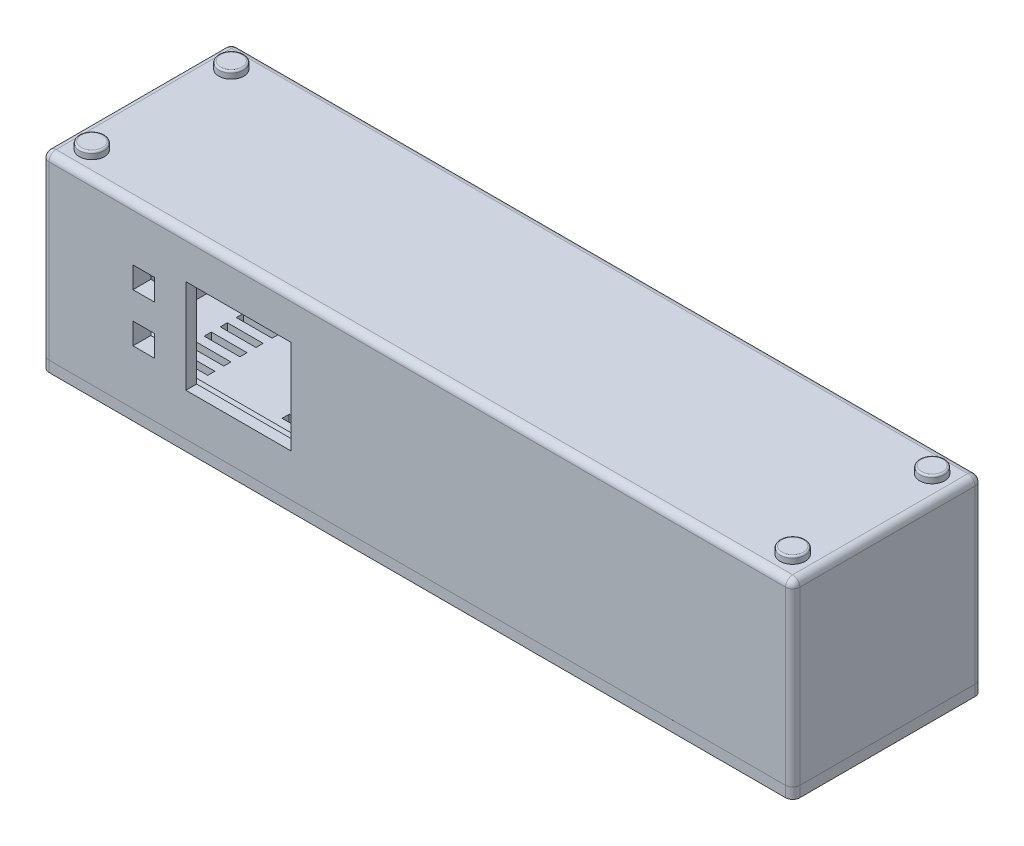
SolidWorks part; units mm, degrees
material "PET"
ref_plane "Спереди" through (0, 0, 0) normal (0, 0, 1) x (1, 0, 0)
ref_plane "Сверху" through (0, 0, 0) normal (0, 1, 0) x (1, 0, 0)
ref_plane "Справа" through (0, 0, 0) normal (1, 0, 0) x (0, 0, -1)
other "Configuration Table"
sketch "Основание & крышка" plane through (0, 0, 0) normal (0, 1, 0) x (1, 0, 0)
  line L1 (105, -26.5) -> (-105, -26.5)
  line L2 (105, -26.5) -> (105, 26.5)
  line L3 (105, 26.5) -> (-105, 26.5)
  line L4 (-105, -26.5) -> (-105, 26.5)
  line L5 (105, -26.5) -> (-105, 26.5) construction
  line L6 (105, 26.5) -> (-105, -26.5) construction
  line L7 (100, -21.5) -> (-100, -21.5)
  line L8 (100, -21.5) -> (100, 21.5)
  line L9 (100, 21.5) -> (-100, 21.5)
  line L10 (-100, -21.5) -> (-100, 21.5)
  line L11 (100, -21.5) -> (-100, 21.5) construction
  line L12 (100, 21.5) -> (-100, -21.5) construction
  point P0 (0, 0)
  point P5 (0, 0)
  dimension "D1" = 210
  dimension "D2" = 53
  dimension "D3" = 43
  dimension "D4" = 200
extrude "Бобышка-Вытянуть1" add sketch "Основание & крышка" along normal blind 50 contours L3 L4 L1 L2
sketch "Эскиз3" plane through (0, 0, 0) normal (0, -1, 0) x (1, 0, 0)
  line L0 (105, 26.5) -> (-105, 26.5) construction
  line L1 (-100, -21.5) -> (100, -21.5)
  line L2 (-100, -21.5) -> (-100, 21.5)
  line L3 (-100, 21.5) -> (100, 21.5)
  line L4 (100, -21.5) -> (100, 21.5)
  line L5 (-100, -21.5) -> (100, 21.5) construction
  line L6 (-100, 21.5) -> (100, -21.5) construction
  line L7 (105, 26.5) -> (105, -26.5) construction
  point P0 (0, 0)
  dimension "D1" = 5
  dimension "D2" = 5
extrude "Вырез-Вытянуть1" cut sketch "Эскиз3" against normal blind 45
sketch "Эскиз4" plane through (0, 50, 0) normal (0, 1, 0) x (1, 0, 0)
  line L0 (0, 41.131) -> (0, -55.5904) construction
  line L1 (105, 26.5) -> (-105, 26.5) construction
  line L2 (105, -26.5) -> (105, 26.5) construction
  line L3 (-127.2033, 0) -> (126.8125, 0) construction
  circle A0 centre (98, 19.5) radius 3.5
  circle A1 centre (-98, 19.5) radius 3.5
  circle A2 centre (98, -19.5) radius 3.5
  circle A3 centre (-98, -19.5) radius 3.5
  dimension "D1" = 7
  dimension "D3" = 7
  dimension "D2" = 7
sketch "Эскиз6" plane through (0, 50, 0) normal (0, 1, 0) x (1, 0, 0)
  line L0 (-117.6289, 0) -> (122.9046, 0) construction
  line L1 (0, 47.7745) -> (0, -57.5444) construction
extrude "Бобышка-Вытянуть2" add sketch "Эскиз4" along normal blind 2 draft 1 contours A0
fillet "Скругление2" radius 0.5 1 edges at (98, 52, -16.0349)
extrude "Бобышка-Вытянуть3" add sketch "Эскиз4<5>" along normal blind 2 contours A2
sketch "Эскиз4<5>" plane through (0, 50, 0) normal (0, 1, 0) x (1, 0, 0) same geometry as "Эскиз4"
extrude "Бобышка-Вытянуть4" add sketch "Эскиз4<6>" along normal blind 2 contours A3
sketch "Эскиз4<6>" plane through (0, 50, 0) normal (0, 1, 0) x (1, 0, 0) same geometry as "Эскиз4"
extrude "Бобышка-Вытянуть5" add sketch "Эскиз4<7>" along normal blind 2 contours A1
sketch "Эскиз4<7>" plane through (0, 50, 0) normal (0, 1, 0) x (1, 0, 0) same geometry as "Эскиз4"
fillet "Скругление3" radius 0.5 1 edges at (-98, 52, 23)
fillet "Скругление4" radius 0.5 1 edges at (-98, 52, -23)
fillet "Скругление5" radius 0.5 1 edges at (98, 52, 16)
sketch "Эскиз7" plane through (0, 0, -26.5) normal (0, 0, -1) x (-1, 0, 0)
  line L0 (0, -32.9698) -> (0, 82.1336) construction
  line L1 (-136.416, 24.5819) -> (136.5704, 24.5819) construction
  circle A0 centre (0, 35.0819) radius 6
  point P7 (0, 24.5819)
  dimension "D1" = 12
  dimension "D2" = 10.5
extrude "Вырез-Вытянуть2" cut sketch "Эскиз7" against normal blind 14 draft 5 contours A0
fillet "Скругление6" radius 2 1 edges at (-6, 35.0819, -26.5)
sketch "Эскиз8" plane through (0, 0, -21.5) normal (0, 0, 1) x (1, 0, 0)
  circle A0 centre (0, 35.0819) radius 7
  dimension "D1" = 14
extrude "Бобышка-Вытянуть6" add sketch "Эскиз8" along normal blind 7 draft 5 contours A0
sketch "Эскиз9" plane through (0, 0, -14.5) normal (0, 0, 1) x (1, 0, 0)
  circle A0 centre (0, 35.0819) radius 5.15
  dimension "D1" = 10.3
extrude "Вырез-Вытянуть3" cut sketch "Эскиз9" against normal blind 7 draft 5 draft outward yes
sketch "Эскиз10" plane through (0, 0, 26.5) normal (0, 0, 1) x (1, 0, 0)
  line L0 (0, -14.7722) -> (0, 61.6389) construction
  line L1 (-118.5615, 25) -> (116.6086, 25) construction
  line L2 (-127.2033, 50) -> (126.8125, 50) construction
  line L3 (-64.7, 38.15) -> (-35.3, 38.15)
  line L4 (-64.7, 38.15) -> (-64.7, 11.85)
  line L5 (-64.7, 11.85) -> (-35.3, 11.85)
  line L6 (-35.3, 38.15) -> (-35.3, 11.85)
  line L7 (-64.7, 38.15) -> (-35.3, 11.85) construction
  line L8 (-64.7, 11.85) -> (-35.3, 38.15) construction
  point P5 (-50, 25)
  point P13 (0, 25)
  dimension "D1" = 29.4
  dimension "D2" = 26.3
  dimension "D3" = 50
  dimension "D4" = 25
extrude "Вырез-Вытянуть4" cut sketch "Эскиз10" against normal blind 5
sketch "Эскиз13" plane through (0, 0, 21.5) normal (0, 0, -1) x (-1, 0, 0)
  line L0 (100, 45) -> (100, 0) construction
  line L1 (30.4, 38.75) -> (69.6, 38.75)
  line L2 (30.4, 38.75) -> (30.4, 11.25)
  line L3 (30.4, 11.25) -> (69.6, 11.25)
  line L4 (69.6, 38.75) -> (69.6, 11.25)
  line L5 (30.4, 38.75) -> (69.6, 11.25) construction
  line L6 (30.4, 11.25) -> (69.6, 38.75) construction
  line L8 (-100, 45) -> (100, 45) construction
  point P0 (50, 25)
  dimension "D1" = 50
  dimension "D2" = 20
  dimension "D3" = 27.5
  dimension "D4" = 39.2
extrude "Вырез-Вытянуть5" cut sketch "Эскиз13" against normal blind 2
sketch "Эскиз14" plane through (0, 0, 26.5) normal (0, 0, 1) x (1, 0, 0)
  line L0 (0, 0) -> (0, 50) construction
  line L1 (105, 0) -> (-105, 0) construction
  line L2 (105, 50) -> (-105, 50) construction
  line L3 (-105, 25) -> (105, 25) construction
  line L4 (-105, 50) -> (-105, 0) construction
  line L5 (105, 50) -> (105, 0) construction
  line L6 (-79.5, 28.8) -> (-73.5, 28.8)
  line L7 (-79.5, 15.2) -> (-73.5, 15.2)
  line L8 (-79.5, 15.2) -> (-79.5, 21.2)
  line L9 (-79.5, 21.2) -> (-73.5, 21.2)
  line L10 (-73.5, 15.2) -> (-73.5, 21.2)
  line L11 (-79.5, 15.2) -> (-73.5, 21.2) construction
  line L12 (-79.5, 21.2) -> (-73.5, 15.2) construction
  line L13 (-79.5, 28.8) -> (-73.5, 34.8) construction
  line L14 (-79.5, 34.8) -> (-79.5, 28.8)
  line L15 (-79.5, 34.8) -> (-73.5, 28.8) construction
  line L16 (-73.5, 34.8) -> (-73.5, 28.8)
  line L17 (-79.5, 34.8) -> (-73.5, 34.8)
  point P12 (-76.5, 18.2)
  point P21 (-76.5, 31.8)
  dimension "D1" = 6
  dimension "D2" = 6
  dimension "D3" = 18.2
  dimension "D4" = 25.5
extrude "Вырез-Вытянуть6" cut sketch "Эскиз14" against normal blind 5
sketch "Эскиз16" plane through (0, 0, 21.5) normal (0, 0, -1) x (-1, 0, 0)
  line L0 (-100, 45) -> (100, 45) construction
  line L1 (73.4, 34.85) -> (79.5, 34.85)
  line L2 (73.4, 34.85) -> (73.4, 28.75)
  line L3 (73.4, 28.75) -> (79.5, 28.75)
  line L4 (79.5, 34.85) -> (79.5, 28.75)
  line L5 (73.4, 34.85) -> (79.5, 28.75) construction
  line L6 (73.4, 28.75) -> (79.5, 34.85) construction
  line L7 (100, 45) -> (100, 0) construction
  point P0 (76.45, 31.8)
  dimension "D1" = 6.1
  dimension "D2" = 6.1
  dimension "D3" = 13.2
  dimension "D4" = 20.5
fillet "Скругление7" radius 2 8 edges at (-105, 25, -26.5) (-105, 50, 0) (0, 50, -26.5) (105, 25, -26.5) (105, 50, 0) (105, 25, 26.5) (-105, 25, 26.5) (0, 50, 26.5)
sketch "Эскиз17" plane through (0, 0, 0) normal (0, -1, 0) x (1, 0, 0)
  line L4 (-105, 24.5) -> (-105, -24.5)
  line L5 (-103, -26.5) -> (103, -26.5)
  line L6 (105, -24.5) -> (105, 24.5)
  line L7 (103, 26.5) -> (-103, 26.5)
  line L8 (-105, 24.5) -> (-105, -24.5)
  line L9 (-103, -26.5) -> (103, -26.5)
  line L10 (105, -24.5) -> (105, 24.5)
  line L11 (103, 26.5) -> (-103, 26.5)
  arc A4 (-105, -24.5) -> (-103, -26.5) centre (-103, -24.5) ccw
  arc A5 (103, -26.5) -> (105, -24.5) centre (103, -24.5) ccw
  arc A6 (105, 24.5) -> (103, 26.5) centre (103, 24.5) ccw
  arc A7 (-103, 26.5) -> (-105, 24.5) centre (-103, 24.5) ccw
  arc A8 (-105, -24.5) -> (-103, -26.5) centre (-103, -24.5) ccw
  arc A9 (103, -26.5) -> (105, -24.5) centre (103, -24.5) ccw
  arc A10 (105, 24.5) -> (103, 26.5) centre (103, 24.5) ccw
  arc A11 (-103, 26.5) -> (-105, 24.5) centre (-103, 24.5) ccw
  dimension "D1" = 0
extrude "Бобышка-Вытянуть8" add sketch "Эскиз17" along normal blind 3 separate body
sketch "Эскиз18" plane through (0, 0, 0) normal (0, 1, 0) x (1, 0, 0)
  line L8 (-100, -21.5) -> (100, -21.5)
  line L28 (-100, -21.5) -> (100, -21.5)
  line L32 (100, -21.5) -> (100, 21.5)
  line L34 (100, -21.5) -> (100, 21.5)
  line L36 (100, 21.5) -> (-100, 21.5)
  line L37 (100, 21.5) -> (-100, 21.5)
  line L38 (-100, 21.5) -> (-100, -21.5)
  line L39 (-100, 21.5) -> (-100, -21.5)
  dimension "D1" = 5
extrude "Крышка" add sketch "Эскиз18" along normal blind 3 from surface thin contours L37 L39 L28 L34 starting at face at (0, 0, 0) thin type one direction reverse wall 3
sketch "Эскиз20" plane through (0, -3, 0) normal (0, -1, 0) x (1, 0, 0)
  line L0 (-105, 0) -> (105, 0) construction
  line L1 (-105, 24.5) -> (-105, -24.5) construction
  line L2 (105, -24.5) -> (105, 24.5) construction
  line L3 (0, 26.5) -> (0, -26.5) construction
  line L4 (103, 26.5) -> (-103, 26.5) construction
  line L5 (-103, -26.5) -> (103, -26.5) construction
sketch "Эскиз21" plane through (0, -3, 0) normal (0, -1, 0) x (1, 0, 0)
  line L0 (-66.7, -49.4791) -> (-66.7, 41.6381) construction
  line L1 (-33.4, -45.2678) -> (-33.4, 45.8494) construction
  line L2 (33.4, -44.7574) -> (33.4, 46.3598) construction
  line L3 (66.7, -45.7783) -> (66.7, 45.3389) construction
  line L4 (105, -24.5) -> (105, 24.5) construction
  line L5 (0, 26.5) -> (0, -26.5) construction
  line L6 (0, -41.131) -> (0, 55.5904) construction
  line L7 (15.5, 60.8548) -> (15.5, -34.3859) construction
  line L8 (10.5, 21.5) -> (20.5, 21.5)
  line L9 (10.5, 21.5) -> (10.5, 19.5)
  line L10 (10.5, 19.5) -> (20.5, 19.5)
  line L11 (20.5, 21.5) -> (20.5, 19.5)
  line L12 (10.5, 21.5) -> (20.5, 19.5) construction
  line L13 (10.5, 19.5) -> (20.5, 21.5) construction
  line L26 (103, 26.5) -> (-103, 26.5) construction
  line L27 (-10.5, 19.5) -> (-20.5, 21.5) construction
  line L28 (-10.5, 21.5) -> (-20.5, 19.5) construction
  line L33 (-20.5, 21.5) -> (-20.5, 19.5)
  line L34 (-10.5, 19.5) -> (-20.5, 19.5)
  line L39 (-10.5, 21.5) -> (-10.5, 19.5)
  line L40 (-10.5, 21.5) -> (-20.5, 21.5)
  line L45 (-56.3, 21.5) -> (-46.3, 19.5) construction
  line L46 (-56.3, 19.5) -> (-46.3, 21.5) construction
  line L51 (-56.3, 21.5) -> (-46.3, 21.5)
  line L52 (-56.3, 21.5) -> (-56.3, 19.5)
  line L57 (-56.3, 19.5) -> (-46.3, 19.5)
  line L58 (-46.3, 21.5) -> (-46.3, 19.5)
  line L63 (-77.1, 19.5) -> (-87.1, 21.5) construction
  line L64 (-77.1, 21.5) -> (-87.1, 19.5) construction
  line L69 (-87.1, 21.5) -> (-87.1, 19.5)
  line L70 (-77.1, 19.5) -> (-87.1, 19.5)
  line L75 (-77.1, 21.5) -> (-77.1, 19.5)
  line L76 (-77.1, 21.5) -> (-87.1, 21.5)
  line L78 (77.3, 21.5) -> (87.3, 19.5) construction
  line L79 (77.3, 19.5) -> (87.3, 21.5) construction
  line L80 (56.3, 19.5) -> (46.3, 21.5) construction
  line L81 (56.3, 21.5) -> (46.3, 19.5) construction
  line L82 (77.3, 21.5) -> (87.3, 21.5)
  line L83 (77.3, 21.5) -> (77.3, 19.5)
  line L84 (77.3, 19.5) -> (87.3, 19.5)
  line L85 (87.3, 21.5) -> (87.3, 19.5)
  line L86 (46.3, 21.5) -> (46.3, 19.5)
  line L87 (56.3, 19.5) -> (46.3, 19.5)
  line L88 (56.3, 21.5) -> (56.3, 19.5)
  line L89 (56.3, 21.5) -> (46.3, 21.5)
  line L198 (0, 55.5904) -> (0, -41.131) construction
  point P14 (15.5, 20.5)
  point P23 (-15.5, 20.5)
  point P28 (-51.3, 20.5)
  point P31 (15.5, 21.5)
  point P38 (-82.1, 20.5)
  point P47 (82.3, 20.5)
  point P48 (51.3, 20.5)
  dimension "D1" = 38.3
  dimension "D2" = 33.3
  dimension "D3" = 33.4
  dimension "D4" = 33.4
  dimension "D5" = 33.3
  dimension "D6" = 15.5
  dimension "D7" = 10
  dimension "D8" = 2
  dimension "D9" = 5
extrude "Вырез-Вытянуть12" cut sketch "Эскиз21" against normal blind 5
pattern_linear "Линейный массив1" count 10 spacing 4.5 along (0, 0, -1) of "Вырез-Вытянуть12"
